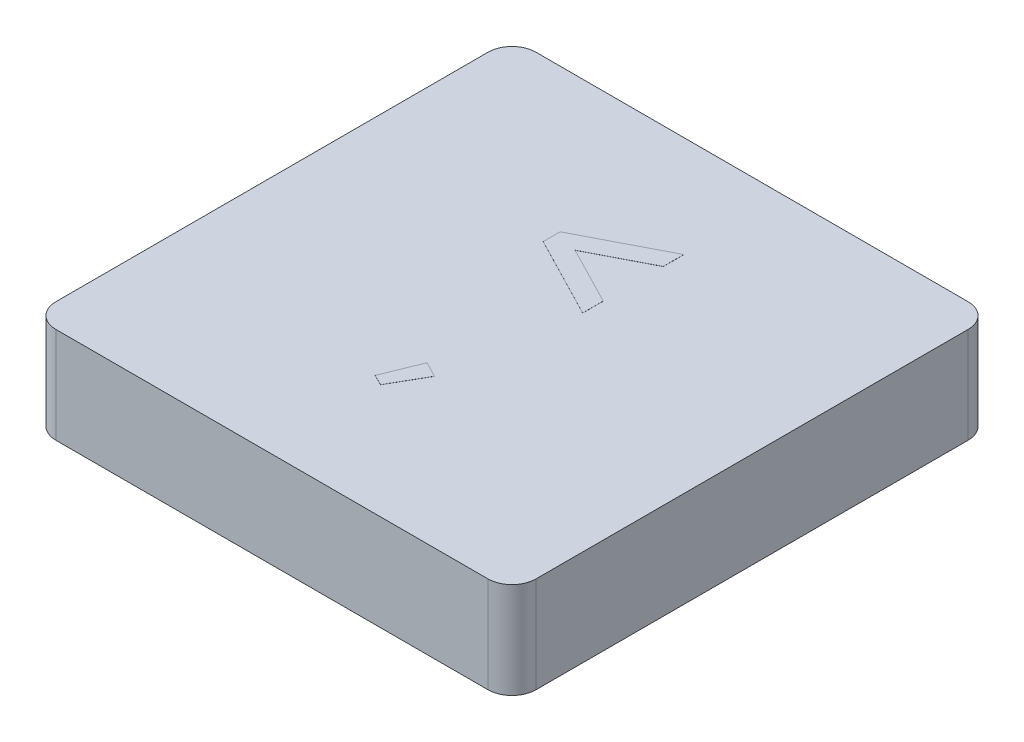
SolidWorks part; units mm, degrees
ref_plane "Front Plane" through (0, 0, 0) normal (0, 0, 1) x (1, 0, 0)
ref_plane "Top Plane" through (0, 0, 0) normal (0, 1, 0) x (1, 0, 0)
ref_plane "Right Plane" through (0, 0, 0) normal (1, 0, 0) x (0, 0, -1)
sketch "Sketch1" plane through (0, 0, 0) normal (0, 1, 0) x (1, 0, 0)
  line L0 (0, 0) -> (12.7, 0)
  line L1 (12.7, 0) -> (12.7, 12.7)
  line L2 (12.7, 12.7) -> (0, 12.7)
  line L3 (0, 12.7) -> (0, 0)
  dimension "D1" = 12.7
  dimension "D2" = 12.7
extrude "Boss-Extrude1" add sketch "Sketch1" along normal blind 2.54
fillet "Fillet1" radius 0.635 4 edges at (0, 1.27, -12.7) (12.7, 1.27, -12.7) (12.7, 1.27, 0) (0, 1.27, 0)
shell "Shell1" thickness 0.635 removed face at (6.35, 0, -6.35)
sketch "Sketch2" plane through (0, 1.905, 0) normal (0, -1, 0) x (-1, 0, 0)
  line L0 (-0.635, 6.35) -> (-12.065, 6.35) construction
  line L1 (-0.635, 12.065) -> (-0.635, 0.635) construction
  line L2 (-12.065, 0.635) -> (-12.065, 12.065) construction
  line L3 (-6.35, 0.635) -> (-6.35, 12.065) construction
  line L4 (-0.635, 0.635) -> (-12.065, 0.635) construction
  line L5 (-12.065, 12.065) -> (-0.635, 12.065) construction
  circle A0 centre (-6.35, 6.35) radius 2.54
  dimension "D1" = 5.08
extrude "Boss-Extrude2" add sketch "Sketch2" along normal up to surface (1.905 mm away) up to face at (6.35, 0, -6.35)
sketch "Sketch3" plane through (0, 2.54, 0) normal (0, 1, 0) x (1, 0, 0)
  line L0 (0.635, 0) -> (12.065, 0) construction
  line L1 (0, 12.065) -> (0, 0.635) construction
  line L2 (12.065, 12.7) -> (0.635, 12.7) construction
  text T0 "<b><</b>"
  text T1 "<b>,</b>"
  dimension "D1" = 3.556
  dimension "D2" = 5.7404
  dimension "D3" = 5.588
  dimension "D4" = 4.826
extrude "Boss-Extrude3" add sketch "Sketch3" along normal blind 0.0025
